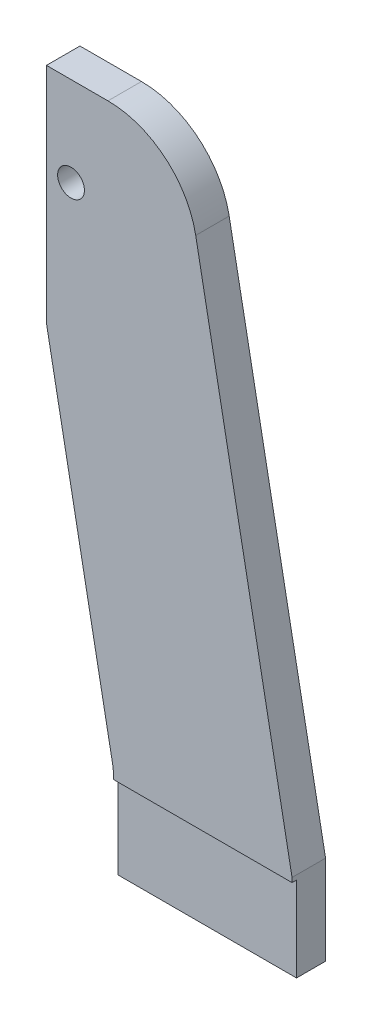
SolidWorks part; units mm, degrees
ref_plane "Alzado" through (0, 0, 0) normal (0, 0, 1) x (1, 0, 0)
ref_plane "Planta" through (0, 0, 0) normal (0, 1, 0) x (1, 0, 0)
ref_plane "Vista lateral" through (0, 0, 0) normal (1, 0, 0) x (0, 0, -1)
sketch "Croquis1" plane through (0, 0, 0) normal (0, 0, 1) x (1, 0, 0)
  line L0 (80, 0) -> (80, 40)
  line L1 (-30, 300) -> (-2.4542, 300)
  line L2 (-30, 300) -> (-30, 200)
  line L3 (0, 0) -> (80, 0)
  line L4 (36.8447, 267.4562) -> (80, 40)
  line L9 (-30, 200) -> (-0.3505, 43.7281)
  line L11 (0, 40) -> (0, 0)
  arc A2 (36.8447, 267.4562) -> (-2.4542, 300) centre (-2.4542, 260) ccw
  arc A3 (-0.3505, 43.7281) -> (0, 40) centre (-20, 40) cw
  dimension "D7" = 40
  dimension "D9" = 40
  dimension "D4" = 20
  dimension "D1" = 30
  dimension "D2" = 300
  dimension "D3" = 80
  dimension "D5" = 100
  dimension "D6" = 40
extrude "Saliente-Extruir1" add sketch "Croquis1" along normal blind 15
sketch "Croquis2" plane through (0, 0, 0) normal (0, 0, -1) x (-1, 0, 0)
  line L0 (2.4542, 300) -> (30, 300) construction
  line L2 (30, 300) -> (30, 200) construction
  circle A0 centre (19, 260) radius 6
  dimension "D3" = 12
  dimension "D1" = 40
  dimension "D2" = 11
extrude "Cortar-Extruir1" cut sketch "Croquis2" against normal through all
hole_wizard "Perforador para roscar para macho de roscar para M44" positions "Croquis7" profile "Croquis8" hole size "M4" standard "DIN"
sketch "Croquis7" plane through (0, 0, 0) normal (0, 0, -1) x (-1, 0, 0)
  line L0 (19, 278.25) -> (19, 241.75)
  circle A0 centre (19, 260) radius 6 construction
  point P10 (19, 278.25)
  point P12 (19, 241.75)
  dimension "D1" = 18.25
  dimension "D2" = 18.25
sketch "Croquis8" plane through (-19, 241.75, 0) normal (1, 0, 0) x (0, 1, 0)
  line L0 (0, 0) -> (0, 7.9914)
  line L1 (0, 7.9914) -> (1.65, 7)
  line L2 (1.65, 7) -> (1.65, 0)
  line L5 (1.65, 0) -> (0, 0)
  line L10 (0, 7.9914) -> (-1.65, 7) construction
  line L11 (0, -6.35) -> (0, 107.95) construction
  dimension "Diámetro de taladro" = 3.3
  dimension "Profundidad de taladro" = 7
  dimension "Ángulo de perforador" = 118
sketch "Croquis9" plane through (0, 0, 15) normal (0, 0, 1) x (1, 0, 0)
  line L1 (0, 0) -> (80, 0)
  line L2 (0, 0) -> (0, 38)
  line L3 (0, 38) -> (80, 38)
  line L4 (80, 0) -> (80, 38)
  dimension "D1" = 80
  dimension "D2" = 38
extrude "Cortar-Extruir2" cut sketch "Croquis9" against normal blind 2
